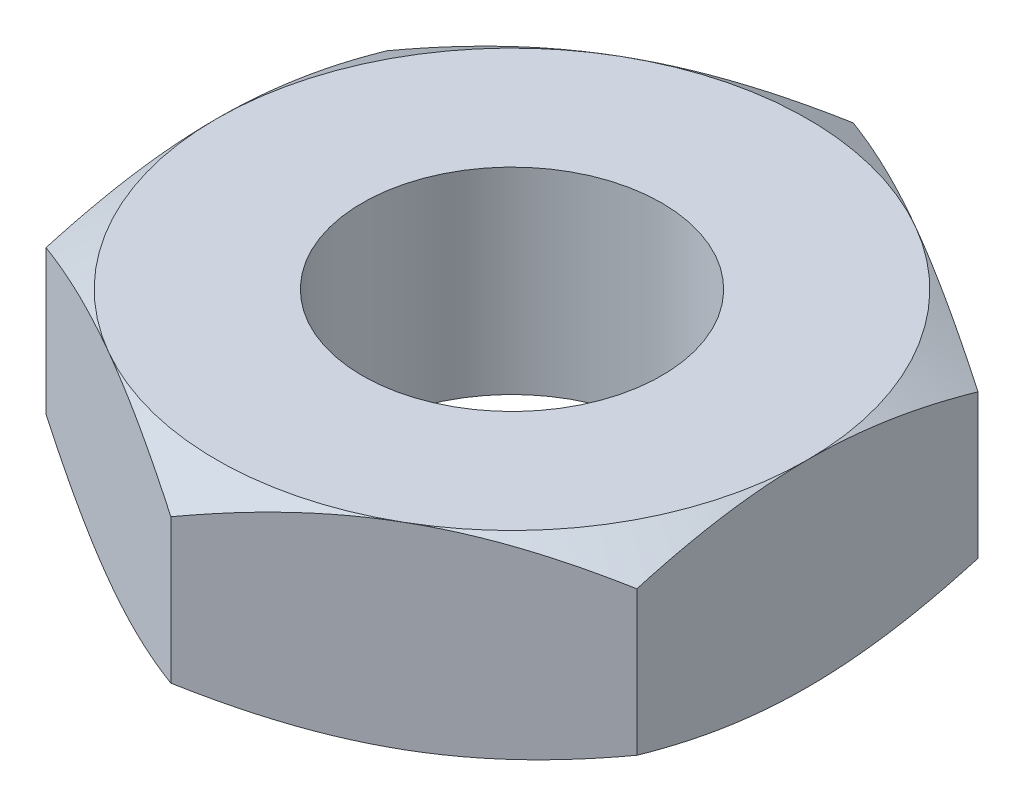
SolidWorks part; units mm, degrees
ref_plane "Front Plane" through (0, 0, 0) normal (0, 0, 1) x (1, 0, 0)
ref_plane "Top Plane" through (0, 0, 0) normal (0, 1, 0) x (1, 0, 0)
ref_plane "Right Plane" through (0, 0, 0) normal (1, 0, 0) x (0, 0, -1)
sketch "Sketch7" plane through (0, 0, 0) normal (0, 1, 0) x (1, 0, 0)
  line L0 (-4.7625, 0) -> (4.7625, 0) construction
  line L1 (-2.413, 0) -> (2.413, 0) construction
  line L2 (-4.7625, 0) -> (-4.7625, -1.0583) construction
  point P4 (0, 0)
  point P8 (0, 0)
sketch "Sketch6" plane through (0, 0, 0) normal (1, 0, 0) x (0, 0, -1)
  line L0 (0, 1.5875) -> (0, -1.5875) construction
  point P4 (0, 0)
sketch "Sketch1" plane through (0, 0, 0) normal (0, 1, 0) x (1, 0, 0)
  line L1 (-4.7625, 2.7496) -> (-4.7625, -2.7496)
  line L2 (-4.7625, -2.7496) -> (0, -5.4993)
  line L3 (0, -5.4993) -> (4.7625, -2.7496)
  line L4 (4.7625, -2.7496) -> (4.7625, 2.7496)
  line L5 (4.7625, 2.7496) -> (0, 5.4993)
  line L6 (0, 5.4993) -> (-4.7625, 2.7496)
  circle A0 centre (0, 0) radius 4.7625 construction
  circle A1 centre (0, 0) radius 2.413
extrude "Boss-Extrude1" add sketch "Sketch1" along normal mid plane 3.175
sketch "Sketch5" plane through (0, 1.5875, 0) normal (0, 1, 0) x (1, 0, 0)
  circle A0 centre (0, 0) radius 4.7625 construction
  circle A1 centre (0, 0) radius 4.7625
extrude "Cut-Extrude2" cut sketch "Sketch5" against normal through all draft 60 flip side to cut
mirror "Mirror1" about plane through (0, 0, 0) normal (0, 1, 0) of "Cut-Extrude2"
sketch "Sketch14" plane through (0, 1.5875, 0) normal (0, 1, 0) x (1, 0, 0)
  line L0 (-2.413, 0) -> (2.413, 0) construction
  line L1 (0, 2.413) -> (0, -2.413) construction
  circle A0 centre (0, 0) radius 2.413 construction
  point P7 (0, 0)
  point P11 (0, 0)
  point P12 (0, -2.413)
  point P13 (-2.413, 0)
  point P14 (0, 2.413)
  point P15 (2.413, 0)
sketch "Sketch8" [suppressed] plane through (0, 1.5875, 0) normal (0, 1, 0) x (1, 0, 0)
  circle A0 centre (0, 0) radius 2.413 construction
  circle A1 centre (0, 0) radius 2.413
extrude "Boss-Extrude2" [suppressed] add sketch "Sketch8" against normal up to surface (3.175 mm away) separate body up to face at (0, -1.5875, 0)
sketch "Sketch9" [suppressed] plane through (0, 1.5875, 0) normal (0, 1, 0) x (1, 0, 0)
  circle A0 centre (0, 0) radius 2.413 construction
  circle A1 centre (0, 0) radius 2.413
extrude "Boss-Extrude3" [suppressed] add sketch "Sketch9" against normal up to surface (3.175 mm away) up to face at (0, -1.5875, 0)
sketch "Sketch10" [suppressed] plane through (0, 1.5875, 0) normal (0, 1, 0) x (1, 0, 0)
  circle A0 centre (0, 0) radius 2.413 construction
  circle A1 centre (0, 0) radius 2.413
curve "Helix/Spiral1" [suppressed] pitch 1.0583 height 4.2333 turns 4
sketch "Sketch11" [suppressed] plane through (0, 0, 0) normal (1, 0, 0) x (0, 0, -1)
  line L0 (-2.413, 1.5875) -> (-2.413, 2.5135)
  line L1 (2.413, 1.5875) -> (-2.413, 1.5875) construction
  line L2 (-2.413, 2.5135) -> (-1.7256, 2.1167)
  line L3 (-1.7256, 2.1167) -> (-1.7256, 1.9844)
  line L4 (-1.7256, 1.9844) -> (-2.413, 1.5875)
  line L5 (-2.413, 2.0505) -> (-1.7256, 2.0505) construction
  line L6 (-2.0693, 2.3151) -> (-2.0693, 1.7859) construction
  spline S0 degree 3 poles (-2.413, 1.5875) (-2.413, 1.5652) (-2.2833, 1.5202) (-1.7301, 1.4531) (-0.9053, 1.3859) (0.0618, 1.3187) (1.0191, 1.2515) (1.8164, 1.1843) (2.3284, 1.1171) (2.4748, 1.0499) (2.2325, 0.9827) (1.6396, 0.9155) (0.7892, 0.8483) (-0.1852, 0.7812) (-1.1304, 0.714) (-1.8981, 0.6468) (-2.3678, 0.5796) (-2.4655, 0.5124) (-2.1761, 0.4452) (-1.5449, 0.378) (-0.6711, 0.3108) (0.3081, 0.2436) (1.2389, 0.1764) (1.9752, 0.1092) (2.4012, 0.042) (2.4502, -0.0252) (2.1143, -0.0924) (1.4464, -0.1596) (0.5514, -0.2268) (-0.4303, -0.294) (-1.3444, -0.3612) (-2.0473, -0.4284) (-2.4287, -0.4956) (-2.4287, -0.5628) (-2.0473, -0.63) (-1.3444, -0.6972) (-0.4303, -0.7644) (0.5514, -0.8315) (1.4464, -0.8987) (2.1143, -0.9659) (2.4502, -1.0331) (2.4012, -1.1003) (1.9752, -1.1675) (1.2389, -1.2347) (0.3081, -1.3019) (-0.6711, -1.3691) (-1.5449, -1.4363) (-2.1761, -1.5035) (-2.4655, -1.5707) (-2.3678, -1.6379) (-1.8981, -1.7051) (-1.1304, -1.7723) (-0.1852, -1.8395) (0.7892, -1.9067) (1.6396, -1.9739) (2.2325, -2.0411) (2.4748, -2.1083) (2.3284, -2.1755) (1.8164, -2.2427) (1.0191, -2.3099) (0.0618, -2.3771) (-0.9053, -2.4442) (-1.7301, -2.5115) (-2.2833, -2.5786) (-2.413, -2.6236) (-2.413, -2.6458) knots 0 0 0 0 0.015873 0.031746 0.047619 0.063492 0.079365 0.095238 0.111111 0.126984 0.142857 0.15873 0.174603 0.190476 0.206349 0.222222 0.238095 0.253968 0.269841 0.285714 0.301587 0.31746 0.333333 0.349206 0.365079 0.380952 0.396825 0.412698 0.428571 0.444444 0.460317 0.47619 0.492063 0.507937 0.52381 0.539683 0.555556 0.571429 0.587302 0.603175 0.619048 0.634921 0.650794 0.666667 0.68254 0.698413 0.714286 0.730159 0.746032 0.761905 0.777778 0.793651 0.809524 0.825397 0.84127 0.857143 0.873016 0.888889 0.904762 0.920635 0.936508 0.952381 0.968254 0.984127 1 1 1 1 construction
  dimension "D1" = 60
  dimension "D2" = 0.1323
  dimension "D3" = 0.5292
sweep "Cut-Sweep1" [suppressed] cut profiles "Sketch11" path "Helix/Spiral1"
combine bodies "Combine1" [suppressed] operation type subtract main body 107 bodies to subtract 108
sketch "Sketch12" [suppressed] plane through (0, 1.5875, 0) normal (0, 1, 0) x (1, 0, 0)
  circle A1 centre (0, 0) radius 2.413
  circle A2 centre (0, 0) radius 2.413
  dimension "D1" = 0
extrude "Cut-Extrude3" [suppressed] cut sketch "Sketch12" against normal through all draft 45
sketch "Sketch13" [suppressed] plane through (0, -1.5875, 0) normal (0, -1, 0) x (1, 0, 0)
  circle A1 centre (0, 0) radius 2.413
  circle A2 centre (0, 0) radius 2.413
  dimension "D1" = 0
extrude "Cut-Extrude4" [suppressed] cut sketch "Sketch13" against normal through all draft 45
equation "\"D3@Helix/Spiral1\"=\"Thickness@Sketch6\"+\"Pitch@Sketch7\""
equation "\"Height@Boss-Extrude1\"=\"Thickness@Sketch6\""
equation "\"D4@Helix/Spiral1\"=\"Pitch@Sketch7\""
equation "\"D2@Sketch11\"=\"Pitch@Sketch7\"*.125"
equation "\"D3@Sketch11\"=\"Pitch@Sketch7\"*.5"
